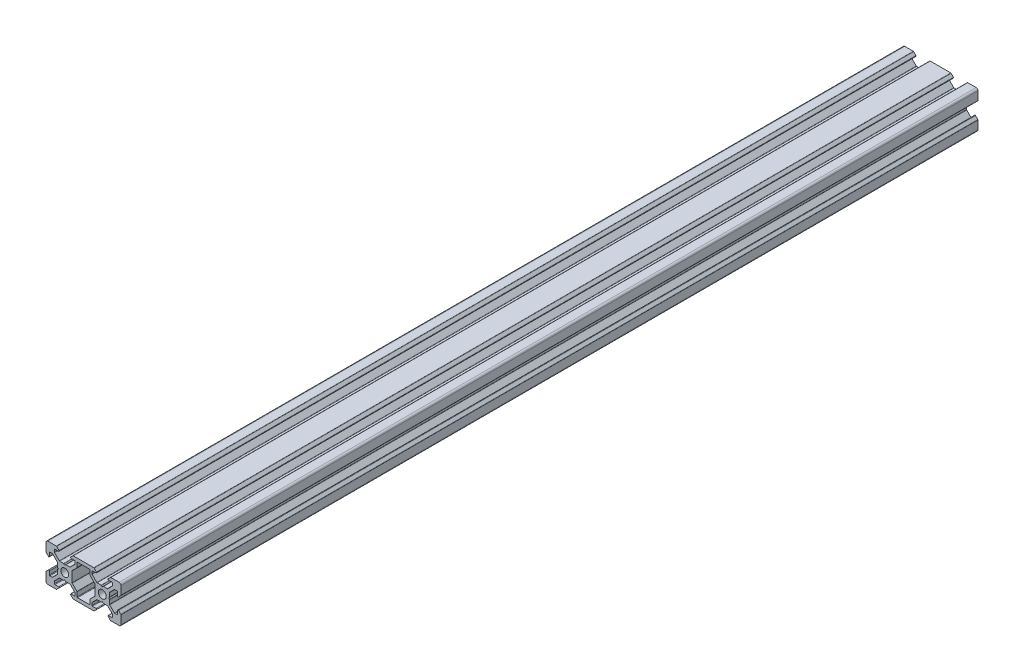
SolidWorks part; units mm, degrees
material "АД31Т ГОСТ 4784-97"
ref_plane "Спереди" through (0, 0, 0) normal (0, 0, 1) x (1, 0, 0)
ref_plane "Сверху" through (0, 0, 0) normal (0, 1, 0) x (1, 0, 0)
ref_plane "Справа" through (0, 0, 0) normal (1, 0, 0) x (0, 0, -1)
sketch "Эскиз1" plane through (0, 0, 0) normal (0, 0, 1) x (1, 0, 0)
  line L0 (12.9654, 0) -> (-12.9654, 0) construction
  line L1 (0, -12.9654) -> (0, 12.9654) construction
  line L2 (0, 0) -> (-18.3359, -18.3359) construction
  line L3 (-10, -10) -> (-10, -4.4)
  line L4 (-10, -4.4) -> (-8.2, -2.6)
  line L5 (-8.2, -2.6) -> (-8.2, -5.4993)
  line L6 (-8.2, -5.4993) -> (-6.56, -5.4993)
  line L7 (-6.56, -5.4993) -> (-3.9007, -2.84)
  line L8 (-3.9007, -2.84) -> (-3.9007, -0.5)
  line L9 (-3.9007, -0.5) -> (-3.4007, 0)
  line L10 (-0.5, -3.9007) -> (0, -3.4007)
  line L11 (-2.84, -3.9007) -> (-0.5, -3.9007)
  line L12 (-5.4993, -6.56) -> (-2.84, -3.9007)
  line L13 (-5.4993, -8.2) -> (-5.4993, -6.56)
  line L14 (-2.6, -8.2) -> (-5.4993, -8.2)
  line L15 (-4.4, -10) -> (-2.6, -8.2)
  line L16 (-10, -10) -> (-4.4, -10)
  line L17 (-10, 10) -> (-4.4, 10)
  line L18 (-4.4, 10) -> (-2.6, 8.2)
  line L19 (-2.6, 8.2) -> (-5.4993, 8.2)
  line L20 (-5.4993, 8.2) -> (-5.4993, 6.56)
  line L21 (-5.4993, 6.56) -> (-2.84, 3.9007)
  line L22 (-2.84, 3.9007) -> (-0.5, 3.9007)
  line L23 (-0.5, 3.9007) -> (0, 3.4007)
  line L24 (-3.9007, 0.5) -> (-3.4007, 0)
  line L25 (-3.9007, 2.84) -> (-3.9007, 0.5)
  line L26 (-6.56, 5.4993) -> (-3.9007, 2.84)
  line L27 (-8.2, 5.4993) -> (-6.56, 5.4993)
  line L28 (-8.2, 2.6) -> (-8.2, 5.4993)
  line L29 (-10, 4.4) -> (-8.2, 2.6)
  line L30 (-10, 10) -> (-10, 4.4)
  line L31 (0.5, 3.9007) -> (0, 3.4007)
  line L32 (0.5, -3.9007) -> (0, -3.4007)
  line L33 (10, -10) -> (10, 10) construction
  line L34 (3.9007, -0.5) -> (3.9007, 0.5)
  line L35 (6.56, -5.4993) -> (6.56, -8.2)
  line L36 (13.44, -5.4993) -> (16.0993, -2.84)
  line L37 (6.56, 5.4993) -> (3.9007, 2.84)
  line L38 (3.9007, 2.84) -> (3.9007, 0.5)
  line L39 (6.56, -8.2) -> (13.44, -8.2)
  line L40 (2.84, 3.9007) -> (0.5, 3.9007)
  line L41 (5.4993, 6.56) -> (2.84, 3.9007)
  line L42 (5.4993, 8.2) -> (5.4993, 6.56)
  line L43 (2.6, 8.2) -> (5.4993, 8.2)
  line L44 (4.4, 10) -> (2.6, 8.2)
  line L45 (15.6, 10) -> (4.4, 10)
  line L46 (15.6, -10) -> (4.4, -10)
  line L47 (4.4, -10) -> (2.6, -8.2)
  line L48 (2.6, -8.2) -> (5.4993, -8.2)
  line L49 (5.4993, -8.2) -> (5.4993, -6.56)
  line L50 (5.4993, -6.56) -> (2.84, -3.9007)
  line L51 (2.84, -3.9007) -> (0.5, -3.9007)
  line L52 (6.56, 5.4993) -> (6.56, 8.2)
  line L53 (3.9007, -2.84) -> (3.9007, -0.5)
  line L54 (6.56, -5.4993) -> (3.9007, -2.84)
  line L55 (16.0993, -2.84) -> (16.0993, -0.5)
  line L56 (6.56, 8.2) -> (13.44, 8.2)
  line L57 (13.44, 5.4993) -> (13.44, 8.2)
  line L58 (17.16, -3.9007) -> (19.5, -3.9007)
  line L59 (14.5007, -6.56) -> (17.16, -3.9007)
  line L60 (14.5007, -8.2) -> (14.5007, -6.56)
  line L61 (17.4, -8.2) -> (14.5007, -8.2)
  line L62 (15.6, -10) -> (17.4, -8.2)
  line L63 (15.6, 10) -> (17.4, 8.2)
  line L64 (17.4, 8.2) -> (14.5007, 8.2)
  line L65 (14.5007, 8.2) -> (14.5007, 6.56)
  line L66 (14.5007, 6.56) -> (17.16, 3.9007)
  line L67 (17.16, 3.9007) -> (19.5, 3.9007)
  line L68 (16.0993, 2.84) -> (16.0993, 0.5)
  line L69 (13.44, 5.4993) -> (16.0993, 2.84)
  line L70 (13.44, -5.4993) -> (13.44, -8.2)
  line L71 (16.0993, -0.5) -> (16.0993, 0.5)
  line L72 (19.5, -3.9007) -> (20, -3.4007)
  line L73 (19.5, 3.9007) -> (20, 3.4007)
  line L74 (30, 10) -> (30, 4.4)
  line L75 (30, 4.4) -> (28.2, 2.6)
  line L76 (28.2, 2.6) -> (28.2, 5.4993)
  line L77 (28.2, 5.4993) -> (26.56, 5.4993)
  line L78 (26.56, 5.4993) -> (23.9007, 2.84)
  line L79 (23.9007, 2.84) -> (23.9007, 0.5)
  line L80 (23.9007, 0.5) -> (23.4007, 0)
  line L81 (20.5, 3.9007) -> (20, 3.4007)
  line L82 (22.84, 3.9007) -> (20.5, 3.9007)
  line L83 (25.4993, 6.56) -> (22.84, 3.9007)
  line L84 (25.4993, 8.2) -> (25.4993, 6.56)
  line L85 (22.6, 8.2) -> (25.4993, 8.2)
  line L86 (24.4, 10) -> (22.6, 8.2)
  line L87 (30, 10) -> (24.4, 10)
  line L88 (30, -10) -> (24.4, -10)
  line L89 (24.4, -10) -> (22.6, -8.2)
  line L90 (22.6, -8.2) -> (25.4993, -8.2)
  line L91 (25.4993, -8.2) -> (25.4993, -6.56)
  line L92 (25.4993, -6.56) -> (22.84, -3.9007)
  line L93 (22.84, -3.9007) -> (20.5, -3.9007)
  line L94 (20.5, -3.9007) -> (20, -3.4007)
  line L95 (23.9007, -0.5) -> (23.4007, 0)
  line L96 (23.9007, -2.84) -> (23.9007, -0.5)
  line L97 (26.56, -5.4993) -> (23.9007, -2.84)
  line L98 (28.2, -5.4993) -> (26.56, -5.4993)
  line L99 (28.2, -2.6) -> (28.2, -5.4993)
  line L100 (30, -4.4) -> (28.2, -2.6)
  line L101 (30, -10) -> (30, -4.4)
  circle A0 centre (0, 0) radius 2.1
  circle A1 centre (20, 0) radius 2.1
  point P62 (10, 8.2)
  point P80 (10, -8.2)
  dimension "D5" = 2.6
  dimension "D10" = 4.2
  dimension "D2" = 10
  dimension "D3" = 1.64
  dimension "D4" = 1.5
  dimension "D6" = 1.8
  dimension "D7" = 2.84
  dimension "D8" = 0.5
  dimension "D9" = 45
extrude "Бобышка-Вытянуть1" add sketch "Эскиз1" along normal blind 457
fillet "Скругление1" radius 1 4 edges at (-10, 10, 228.5) (-10, -10, 228.5) (30, 10, 228.5) (30, -10, 228.5)
fillet "Скругление2" radius 0.3 83 edges at (-4.4, 10, 228.5) (-2.6, 8.2, 228.5) (-5.4993, 8.2, 228.5) (-5.4993, 6.56, 228.5) (-2.84, 3.9007, 228.5) (-0.5, 3.9007, 228.5) (0.5, 3.9007, 228.5) (2.84, 3.9007, 228.5) (5.4993, 6.56, 228.5) (4.4, 10, 228.5) (5.4993, 8.2, 228.5) (2.6, 8.2, 228.5) (3.9007, 2.84, 228.5) (3.9007, -2.84, 228.5) (4.4, -10, 228.5) (2.6, -8.2, 228.5) (5.4993, -8.2, 228.5) (5.4993, -6.56, 228.5) (2.84, -3.9007, 228.5) (0.5, -3.9007, 228.5) (-0.5, -3.9007, 228.5) (-2.84, -3.9007, 228.5) (-5.4993, -6.56, 228.5) (-5.4993, -8.2, 228.5) (-2.6, -8.2, 228.5) (-10, -4.4, 228.5) (-8.2, -2.6, 228.5) (-8.2, -5.4993, 228.5) (-6.56, -5.4993, 228.5) (-3.9007, -2.84, 228.5) (-3.9007, -0.5, 228.5) (-3.9007, 0.5, 228.5) (-3.9007, 2.84, 228.5) (-6.56, 5.4993, 228.5) (-8.2, 5.4993, 228.5) (-8.2, 2.6, 228.5) (-10, 4.4, 228.5) (6.56, -5.4993, 228.5) (6.56, 5.4993, 228.5) (6.56, 8.2, 228.5) (13.44, 8.2, 228.5) (13.44, 5.4993, 228.5) (16.0993, 2.84, 228.5) (16.0993, -2.84, 228.5) (13.44, -5.4993, 228.5) (13.44, -8.2, 228.5) (6.56, -8.2, 228.5) (15.6, 10, 228.5) (17.4, 8.2, 228.5) (14.5007, 8.2, 228.5) (14.5007, 6.56, 228.5) (17.16, 3.9007, 228.5) (19.5, 3.9007, 228.5) (20.5, 3.9007, 228.5) (22.84, 3.9007, 228.5) (25.4993, 6.56, 228.5) (25.4993, 8.2, 228.5) (22.6, 8.2, 228.5) (24.4, 10, 228.5) (30, 4.4, 228.5) (28.2, 2.6, 228.5) (28.2, 5.4993, 228.5) (26.56, 5.4993, 228.5) (23.9007, 2.84, 228.5) (23.9007, 0.5, 228.5) (23.9007, -0.5, 228.5) (23.9007, -2.84, 228.5) (26.56, -5.4993, 228.5) (28.2, -5.4993, 228.5) (28.2, -2.6, 228.5) (30, -4.4, 228.5) (24.4, -10, 228.5) (22.6, -8.2, 228.5) (25.4993, -8.2, 228.5) (25.4993, -6.56, 228.5) (22.84, -3.9007, 228.5) (20.5, -3.9007, 228.5) (19.5, -3.9007, 228.5) (17.16, -3.9007, 228.5) (14.5007, -6.56, 228.5) (14.5007, -8.2, 228.5) (17.4, -8.2, 228.5) (15.6, -10, 228.5)
